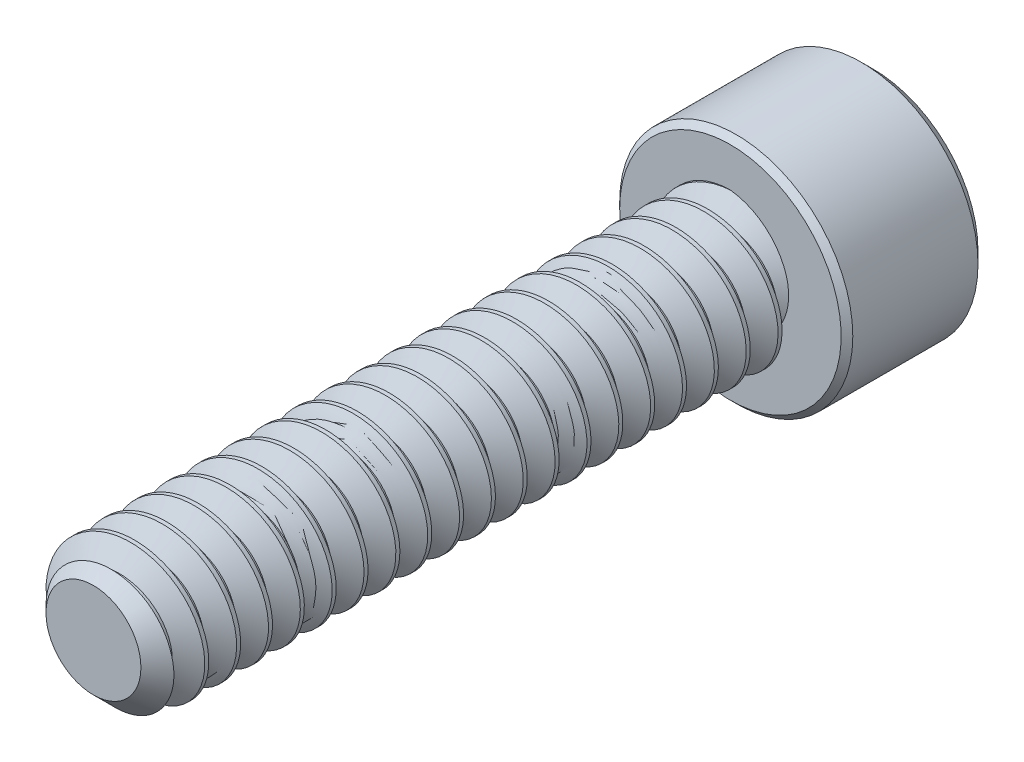
SolidWorks part; units mm, degrees
ref_plane "Front Plane" through (0, 0, 0) normal (0, 0, 1) x (1, 0, 0)
ref_plane "Top Plane" through (0, 0, 0) normal (0, 1, 0) x (1, 0, 0)
ref_plane "Right Plane" through (0, 0, 0) normal (1, 0, 0) x (0, 0, -1)
sketch "Sketch0" plane through (0, 0, 0) normal (1, 0, 0) x (0, 0, -1)
  line L0 (0, 0) -> (12.7, 0) construction
  point P2 (15.5448, 0)
  point P4 (0, 0)
  dimension "D1" = 12.7
  dimension "D2" = 2.8448
  dimension "Min Thread" = 0
sketch "Sketch1" plane through (0, 0, 0) normal (0, 0, 1) x (1, 0, 0)
  circle A0 centre (0, 0) radius 1.4224
  dimension "OD" = 2.8448
extrude "Extrude1" add sketch "Sketch1" against normal blind 12.7
sketch "Sketch2" plane through (0, 0, 0) normal (0, 0, 1) x (1, 0, 0)
  circle A0 centre (0, 0) radius 1.4224 construction
  circle A1 centre (0, 0) radius 1.4224
curve "Helix/Spiral1" pitch 0.635 height 13.335 turns 21 parameters "pitch"=0.635
chamfer "Chamfer3" distance 0.4763 angle 45 1 edges at (1.4224, 0, 0)
sketch "Sketch3" plane through (0, 0, 0) normal (1, 0, 0) x (0, 0, -1)
  line L0 (-0.5556, 1.4224) -> (-0.3175, 1.01)
  line L1 (-0.3175, 1.01) -> (-0.2381, 1.01)
  line L2 (-0.2381, 1.01) -> (0, 1.4224)
  line L3 (-0.5556, 1.4224) -> (0, 1.4224)
  line L4 (-0.2778, 1.4224) -> (-0.2778, 1.01) construction
  line L5 (-0.4366, 1.2162) -> (-0.1191, 1.2162) construction
  line L6 (0, 1.4224) -> (0, -1.4224) construction
  dimension "D1" = 0.0794
  dimension "D2" = 0.3175
  dimension "D3" = 60
sweep "Cut-Sweep1" cut profiles "Sketch3" path "Helix/Spiral1" align with end faces yes
sketch "Sketch5" plane through (0, 0, 0) normal (1, 0, 0) x (0, 0, -1)
  line L0 (12.7, -1.0232) -> (12.7, 1.0149) construction
  line L1 (12.7, 1.4224) -> (0, 1.4224)
  line L2 (12.7, 1.4224) -> (12.7, 0)
  line L3 (12.7, 0) -> (-0.5177, 0)
  line L4 (0, 0) -> (12.7, 0) construction
  line L5 (0, 1.4224) -> (-0.5177, 0)
  line L6 (0, 0) -> (15.24, 0) construction
  dimension "D1" = 70
  dimension "D3" = 2.54
revolve "partially thread" [suppressed] add sketch "Sketch5" angle 360 about L6
sketch "Sketch6" plane through (0, 0, -12.7) normal (0, 0, -1) x (-1, 0, 0)
  circle A0 centre (0, 0) radius 2.3241
  dimension "head dia" = 4.6482
extrude "Extrude2" add sketch "Sketch6" along normal blind 2.8448
sketch "Sketch7" plane through (0, 0, -15.5448) normal (0, 0, -1) x (-1, 0, 0)
  line L1 (0, 1.3748) -> (-1.1906, 0.6874)
  line L2 (-1.1906, 0.6874) -> (-1.1906, -0.6874)
  line L3 (-1.1906, -0.6874) -> (0, -1.3748)
  line L4 (0, -1.3748) -> (1.1906, -0.6874)
  line L5 (1.1906, -0.6874) -> (1.1906, 0.6874)
  line L6 (1.1906, 0.6874) -> (0, 1.3748)
  circle A0 centre (0, 0) radius 1.1906 construction
  dimension "hex dia" = 2.3813
extrude "Cut-Extrude1" cut sketch "Sketch7" against normal blind 1.7859
sketch "Sketch8" plane through (0, 0, -15.5448) normal (0, 0, -1) x (-1, 0, 0)
  circle A0 centre (0, 0) radius 1.3748
extrude "Cut-Extrude2" cut sketch "Sketch8" against normal through all draft 45
chamfer "Chamfer1" distance 0.2324 angle 45 1 edges at (-2.3241, 0, -15.5448)
chamfer "Chamfer2" distance 0.1162 angle 45 1 edges at (-2.3241, 0, -12.7)
sketch "Sketch9" plane through (0, 0, 0) normal (1, 0, 0) x (0, 0, -1)
  line L0 (0, 1.4224) -> (0, -1.4224) construction
  line L1 (1.5875, 1.4224) -> (1.5875, -1.4224) construction
  line L2 (15.5448, 2.3241) -> (15.5448, -2.3241) construction
  line L3 (12.7, 2.3241) -> (12.7, -2.3241) construction
  line L4 (12.7, 2.2079) -> (12.7, -2.2079) construction
  line L5 (15.5448, -2.0917) -> (15.5448, 2.0917) construction
  line L6 (12.7, -2.3241) -> (12.7, 2.3241) construction
  line L7 (0, 0.9462) -> (0, -0.9462) construction
  line L8 (-0.5556, 1.4224) -> (0, 1.4224) construction
  line L9 (1.5875, 0) -> (0, 0) construction
  dimension "D1" = 1.5875
equation "\"D3@Helix/Spiral1\" = \"screw length@Extrude1\"+\"pitch@Helix/Spiral1\""
equation "\"D1@Sketch3\" = \"pitch@Helix/Spiral1\"*.125"
equation "\"D2@Sketch3\" = \"pitch@Helix/Spiral1\"*.5"
equation "\"D1@Cut-Extrude1\" = \"hex dia@Sketch7\"*.75"
equation "\"D1@Chamfer1\" = \"head dia@Sketch6\"*.05"
equation "\"D1@Sketch9\" = \"pitch@Helix/Spiral1\"*2.50"
equation "\"D1@Chamfer2\" = \"D1@Chamfer1\"/2"
equation "\"D1@Chamfer3\" = \"pitch@Helix/Spiral1\"*.750"
equation "\"D1@Sketch0\" = \"screw length@Extrude1\""
equation "\"D2@Sketch0\" = \"head depth@Extrude2\""
